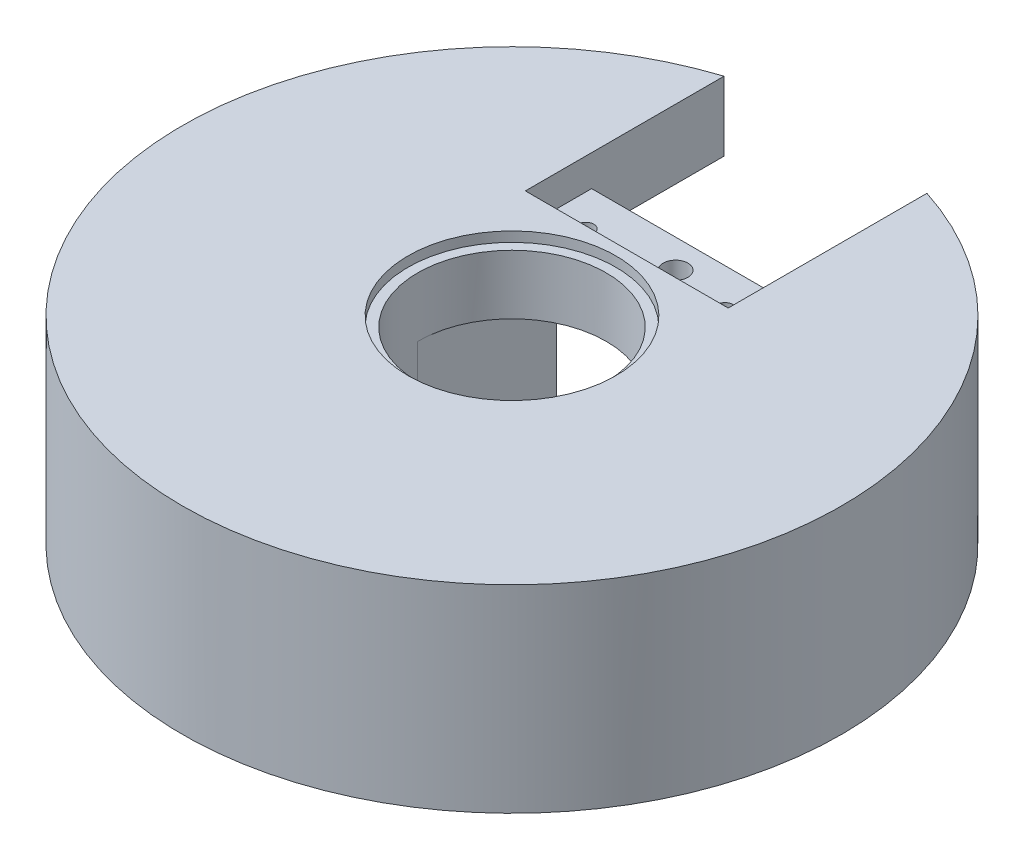
SolidWorks part; units mm, degrees
note: The reader was unsure of these and kept them because the rebuilt part matched: shared geometry of "Sketch6<4>".
other "Markup2"
sketch "Sketch11" plane through (-33.3, 0, -31.6832) normal (-0.1985, -0.3048, -0.9315) x (0.9607, 0.1275, -0.2465)
ref_plane "Front Plane" through (0, 0, 0) normal (0, 0, 1) x (1, 0, 0)
ref_plane "Top Plane" through (0, 0, 0) normal (0, 1, 0) x (1, 0, 0)
ref_plane "Right Plane" through (0, 0, 0) normal (1, 0, 0) x (0, 0, -1)
sketch "Sketch1" plane through (0, 0, 0) normal (0, 1, 0) x (1, 0, 0)
  circle A0 centre (0, 0) radius 33.3
  dimension "D1" = 66.6
extrude "Boss-Extrude1" add sketch "Sketch1" along normal blind 20
sketch "Sketch3" plane through (0, 0, 0) normal (0, -1, 0) x (1, 0, 0)
  line L0 (3.2928, 18) -> (-5.3006, 18) construction
  line L1 (2.5019, 18) -> (-2.5019, 18)
  arc A0 (-2.5019, 18) -> (2.5019, 18) centre (0, 18) ccw
  point P10 (0, 0)
  dimension "D1" = 18
revolve "Cut-Revolve7" cut sketch "Sketch3" angle 360 about L0
pattern_circular "CirPattern1" count 3 over 360 about axis through (0, 0, 0) along (0, 1, 0) of "Cut-Revolve7"
sketch "Sketch5" plane through (0, 0, 0) normal (0, -1, 0) x (1, 0, 0)
  line L0 (-9.525, 0) -> (-9.525, -14)
  line L1 (-9.525, -14) -> (-21.2026, -25.6776)
  line L2 (0, -1.8595) -> (0, 3.43) construction
  line L3 (9.525, 0) -> (9.525, -14)
  line L4 (9.525, -14) -> (21.2026, -25.6776)
  circle A0 centre (0, 0) radius 9.525
  circle A3 centre (0, 0) radius 33.3 construction
  circle A4 centre (0, 0) radius 33.3
  dimension "D1" = 19.05
  dimension "D2" = 14
  dimension "D3" = 135
extrude "Cut-Extrude1" cut sketch "Sketch5" against normal blind 13
sketch "Sketch6" plane through (0, 20, 0) normal (0, 1, 0) x (1, 0, 0)
  circle A0 centre (0, 0) radius 9.525
  circle A1 centre (0, 0) radius 10.5
  dimension "D1" = 19.05
  dimension "D2" = 21
extrude "Cut-Extrude3" cut sketch "Sketch6" against normal up to next contours A0
extrude "Cut-Extrude4" cut sketch "Sketch6<4>" against normal blind 1 contours A1 A0
sketch "Sketch6<4>" plane through (0, 20, 0) normal (0, 1, 0) x (1, 0, 0) same geometry as "Sketch6"
sketch "Sketch7" plane through (0, 20, 0) normal (0, 1, 0) x (1, 0, 0)
  line L0 (-7.03, 14.5) -> (7.03, 14.5) construction
  circle A0 centre (-7.03, 14.5) radius 0.8
  circle A1 centre (7.03, 14.5) radius 0.8
  circle A2 centre (1.13, 15.4) radius 1.25
  point P4 (0, 14.5)
  dimension "D1" = 1.6
  dimension "D4" = 0.9
  dimension "D6" = 2.5
  dimension "D2" = 14.06
  dimension "D3" = 14.5
  dimension "D5" = 5.9
extrude "Cut-Extrude5" cut sketch "Sketch7" against normal through all
sketch "Sketch8" plane through (0, 20, 0) normal (0, 1, 0) x (1, 0, 0)
  line L1 (-10.25, 11.6) -> (10.25, 11.6)
  line L2 (-10.25, 11.6) -> (-10.25, 36.6)
  line L3 (-10.25, 36.6) -> (10.25, 36.6)
  line L4 (10.25, 11.6) -> (10.25, 36.6)
  line L5 (-10.25, 11.6) -> (10.25, 36.6) construction
  line L6 (-10.25, 36.6) -> (10.25, 11.6) construction
  circle A0 centre (-7.03, 14.5) radius 0.8 construction
  point P0 (0, 24.1)
  point P7 (0, 0)
  dimension "D1" = 25
  dimension "D2" = 20.5
  dimension "D3" = 2.9
extrude "Cut-Extrude6" cut sketch "Sketch8" against normal blind 3.15
sketch "Sketch9" plane through (0, 16.85, 0) normal (0, 1, 0) x (1, 0, 0)
  line L0 (10.25, 11.6) -> (10.25, 31.6832) construction
  line L1 (-10.25, 18.3) -> (10.25, 18.3)
  line L2 (-10.25, 18.3) -> (-10.25, 38.3)
  line L3 (-10.25, 38.3) -> (10.25, 38.3)
  line L4 (10.25, 18.3) -> (10.25, 38.3)
  line L5 (-10.25, 18.3) -> (10.25, 38.3) construction
  line L6 (-10.25, 38.3) -> (10.25, 18.3) construction
  line L7 (-10.25, 31.6832) -> (-10.25, 11.6) construction
  circle A0 centre (-7.03, 14.5) radius 0.8 construction
  point P0 (0, 28.3)
  dimension "D1" = 3.8
  dimension "D2" = 20
extrude "Cut-Extrude7" cut sketch "Sketch9" against normal up to next
